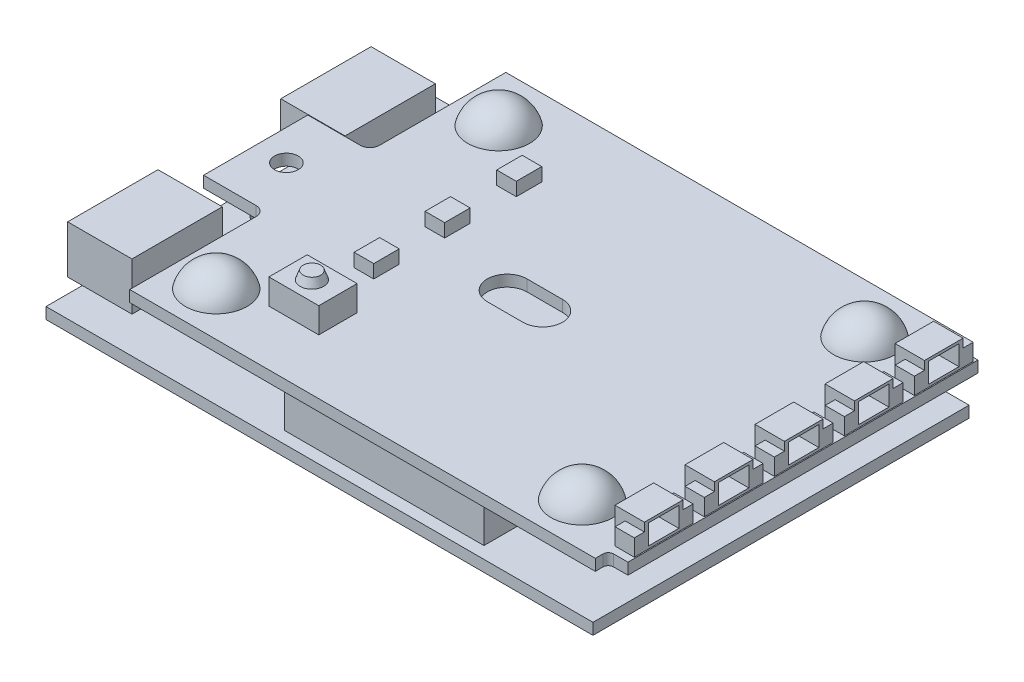
SolidWorks part; units mm, degrees
ref_plane "Front Plane" through (0, 0, 0) normal (0, 0, 1) x (1, 0, 0)
ref_plane "Top Plane" through (0, 0, 0) normal (0, 1, 0) x (1, 0, 0)
ref_plane "Right Plane" through (0, 0, 0) normal (1, 0, 0) x (0, 0, -1)
sketch "Sketch1" plane through (0, 0, 0) normal (0, 1, 0) x (1, 0, 0)
  line L1 (0, 0) -> (77.978, 0)
  line L2 (0, 0) -> (0, -53.6194)
  line L3 (0, -53.6194) -> (77.978, -53.6194)
  line L4 (77.978, 0) -> (77.978, -53.6194)
  dimension "D1" = 77.978
  dimension "D2" = 53.6194
extrude "Bottom Board" add sketch "Sketch1" along normal blind 1.6129
sketch "Sketch2" plane through (0, 1.6129, 0) normal (0, 1, 0) x (-1, 0, 0)
  line L0 (0, 0) -> (0, 53.6194) construction
  line L1 (2.0955, 5.1816) -> (-7.0739, 5.1816)
  line L2 (2.0955, 5.1816) -> (2.0955, 18.0594)
  line L3 (2.0955, 18.0594) -> (-7.0739, 18.0594)
  line L4 (-7.0739, 5.1816) -> (-7.0739, 18.0594)
  line L5 (-77.978, 0) -> (0, 0) construction
  dimension "D1" = 12.8778
  dimension "D2" = 9.1694
  dimension "D3" = 5.1816
  dimension "D4" = 2.0955
extrude "Connector Body" add sketch "Sketch2" along normal blind 6.8199
sketch "Sketch4" plane through (-2.0955, 0, 0) normal (-1, 0, 0) x (0, 0, 1)
  line L0 (5.1816, 8.4328) -> (5.1816, 1.6129) construction
  line L1 (5.7658, 7.8105) -> (8.3947, 7.8105)
  line L2 (5.7658, 7.8105) -> (5.7658, 5.2197)
  line L3 (5.7658, 5.2197) -> (8.3947, 5.2197)
  line L4 (8.3947, 7.8105) -> (8.3947, 5.2197)
  line L5 (5.1816, 8.4328) -> (18.0594, 8.4328) construction
  line L6 (8.7926, 7.8105) -> (8.7926, 5.2197)
  line L7 (8.7926, 5.2197) -> (11.4215, 5.2197)
  line L8 (11.4215, 7.8105) -> (11.4215, 5.2197)
  line L9 (8.7926, 7.8105) -> (11.4215, 7.8105)
  line L10 (11.8195, 7.8105) -> (11.8195, 5.2197)
  line L11 (11.8195, 5.2197) -> (14.4484, 5.2197)
  line L12 (14.4484, 7.8105) -> (14.4484, 5.2197)
  line L13 (11.8195, 7.8105) -> (14.4484, 7.8105)
  line L14 (14.8463, 7.8105) -> (14.8463, 5.2197)
  line L15 (14.8463, 5.2197) -> (17.4752, 5.2197)
  line L16 (17.4752, 7.8105) -> (17.4752, 5.2197)
  line L17 (14.8463, 7.8105) -> (17.4752, 7.8105)
  line L18 (5.7658, 4.826) -> (5.7658, 2.2352)
  line L19 (5.7658, 2.2352) -> (8.3947, 2.2352)
  line L20 (8.3947, 4.826) -> (8.3947, 2.2352)
  line L21 (5.7658, 4.826) -> (8.3947, 4.826)
  line L22 (8.7926, 4.826) -> (8.7926, 2.2352)
  line L23 (8.7926, 2.2352) -> (11.4215, 2.2352)
  line L24 (11.4215, 4.826) -> (11.4215, 2.2352)
  line L25 (8.7926, 4.826) -> (11.4215, 4.826)
  line L26 (11.8195, 4.826) -> (11.8195, 2.2352)
  line L27 (11.8195, 2.2352) -> (14.4484, 2.2352)
  line L28 (14.4484, 4.826) -> (14.4484, 2.2352)
  line L29 (11.8195, 4.826) -> (14.4484, 4.826)
  line L30 (14.8463, 4.826) -> (14.8463, 2.2352)
  line L31 (14.8463, 2.2352) -> (17.4752, 2.2352)
  line L32 (17.4752, 4.826) -> (17.4752, 2.2352)
  line L33 (14.8463, 4.826) -> (17.4752, 4.826)
  line L34 (18.0594, 8.4328) -> (18.0594, 1.6129) construction
  line L35 (17.4752, 7.4085) -> (18.0594, 7.4085) construction
  line L36 (5.7658, 7.5345) -> (5.1816, 7.5345) construction
  line L37 (7.8077, 7.8105) -> (7.8077, 8.4328)
  line L38 (7.8077, 2.2352) -> (7.8077, 1.6129)
  line L39 (5.1816, 1.6129) -> (18.0594, 1.6129) construction
  dimension "D1" = 2.6289
  dimension "D2" = 2.5908
  dimension "D3" = 0.5842
  dimension "D4" = 0.6223
  dimension "D5" = 4
  dimension "D6" = 2
extrude "Connector Holes" cut sketch "Sketch4" against normal blind 5.08 contours L4 L1 L2 L3 | L9 L6 L7 L8 | L13 L10 L11 L12 | L17 L14 L15 L16 | L33 L30 L31 L32 | L29 L26 L27 L28 | L25 L22 L23 L24 | L21 L18 L19 L20 region at (-2.0955, 6.5151, 7.0802) region at (-2.0955, 6.5151, 10.1071) region at (-2.0955, 6.5151, 13.1339) region at (-2.0955, 6.5151, 16.1608) region at (-2.0955, 3.5306, 7.0802) region at (-2.0955, 3.5306, 10.1071) region at (-2.0955, 3.5306, 13.1339) region at (-2.0955, 3.5306, 16.1608)
ref_plane "Center Plane" through (0, 0, 26.8097) normal (0, 0, -1) x (-1, 0, 0)
mirror "Connector Mirror" about plane through (0, 0, 26.8097) normal (0, 0, -1) of "Connector Holes", "Connector Body"
sketch "Sketch5" plane through (0, 1.6129, 0) normal (0, 1, 0) x (1, 0, 0)
  line L0 (77.978, -26.8097) -> (0, -26.8097) construction
  line L1 (77.978, -53.6194) -> (77.978, 0) construction
  line L2 (0, -18.0594) -> (0, -35.56) construction
  line L3 (2.9845, -26.8097) -> (2.9845, -21.4955) construction
  line L4 (36.0172, -26.8097) -> (36.0172, -8.1241) construction
  line L5 (0, -18.0594) -> (0, -35.56) construction
  circle A0 centre (4.68, -26.8097) radius 1.6955
  circle A1 centre (39.0652, -26.8097) radius 3.048
  dimension "D1" = 3.3909
  dimension "D3" = 6.096
  dimension "D2" = 2.9845
  dimension "D4" = 36.0172
extrude "Bottom Board Hole" cut sketch "Sketch5" against normal up to next
sketch "Sketch6" plane through (0, 1.6129, 0) normal (0, 1, 0) x (-1, 0, 0)
  line L0 (-77.978, 0) -> (0, 0) construction
  line L1 (-39.37, 1.7018) -> (-67.818, 1.7018)
  line L2 (-39.37, 1.7018) -> (-39.37, 7.2644)
  line L3 (-39.37, 7.2644) -> (-67.818, 7.2644)
  line L4 (-67.818, 1.7018) -> (-67.818, 7.2644)
  line L5 (-77.978, 53.6194) -> (-77.978, 0) construction
  line L6 (-32.2834, 46.355) -> (-60.7314, 46.355)
  line L7 (-32.2834, 46.355) -> (-32.2834, 51.9176)
  line L8 (-32.2834, 51.9176) -> (-60.7314, 51.9176)
  line L9 (-60.7314, 46.355) -> (-60.7314, 51.9176)
  line L10 (0, 18.0594) -> (0, 35.56) construction
  line L12 (-44.4047, 1.7018) -> (-44.4047, 0) construction
  line L13 (-37.561, 51.9176) -> (-37.561, 53.6194) construction
  line L14 (0, 53.6194) -> (-77.978, 53.6194) construction
  dimension "D1" = 28.448
  dimension "D2" = 5.5626
  dimension "D3" = 1.7018
  dimension "D4" = 10.16
  dimension "D5" = 28.448
  dimension "D6" = 5.5626
  dimension "D7" = 32.2834
extrude "Layer Connectors" add sketch "Sketch6" along normal blind 6.4516
sketch "Sketch7" plane through (0, 8.0645, 0) normal (0, 1, 0) x (1, 0, 0)
  line L0 (77.978, -53.6194) -> (77.978, 0) construction
  line L1 (78.3082, 0) -> (11.938, 0)
  line L2 (81.1022, -1.8542) -> (81.1022, -51.7652)
  line L3 (78.3082, -53.6194) -> (11.938, -53.6194)
  line L4 (11.938, 0) -> (11.938, -18.0086)
  line L5 (0, -18.0594) -> (0, -35.56) construction
  line L6 (77.978, 0) -> (0, 0) construction
  line L7 (0, -53.6194) -> (77.978, -53.6194) construction
  line L8 (15.6034, 0) -> (15.6034, -19.3802) construction
  line L9 (10.5664, -19.3802) -> (3.0861, -19.3802)
  line L10 (11.938, -35.6108) -> (11.938, -53.6194)
  line L11 (10.5664, -34.2392) -> (3.0861, -34.2392)
  line L12 (3.0861, -19.3802) -> (3.0861, -34.2392)
  line L13 (10.5664, -19.3802) -> (15.6034, -19.3802) construction
  line L14 (16.8171, -34.2392) -> (16.8171, -53.6194) construction
  line L15 (10.5664, -34.2392) -> (16.8171, -34.2392) construction
  line L16 (77.978, -26.8097) -> (0, -26.8097) construction
  line L17 (5.7658, -26.8097) -> (5.7658, -22.9762) construction
  line L18 (36.1061, -26.8097) -> (46.8249, -26.8097) construction
  line L19 (38.9318, -23.984) -> (43.9992, -23.984)
  line L20 (36.1061, -26.8097) -> (36.1061, -33.1542) construction
  line L21 (38.9318, -29.6354) -> (43.9992, -29.6355)
  line L22 (78.3082, -53.6194) -> (78.3082, -52.5272)
  line L23 (81.1022, -51.7652) -> (79.0702, -51.7652)
  line L25 (81.1022, -1.8542) -> (79.0702, -1.8542)
  line L26 (78.3082, 0) -> (78.3082, -1.0922)
  arc A0 (11.938, -18.0086) -> (10.5664, -19.3802) centre (10.5664, -18.0086) cw
  arc A1 (10.5664, -34.2392) -> (11.938, -35.6108) centre (10.5664, -35.6108) cw
  circle A2 centre (7.4613, -26.8097) radius 1.6955
  circle A3 centre (4.68, -26.8097) radius 1.6955 construction
  arc A4 (38.9318, -29.6354) -> (38.9318, -23.984) centre (38.9318, -26.8097) cw
  arc A5 (43.9992, -23.984) -> (43.9992, -29.6355) centre (43.9992, -26.8097) cw
  arc A6 (79.0702, -1.8542) -> (78.3082, -1.0922) centre (79.0702, -1.0922) cw
  arc A7 (79.0702, -51.7652) -> (78.3082, -52.5272) centre (79.0702, -52.5272) ccw
  point P45 (78.3082, -1.8542)
  dimension "D5" = 1.3716
  dimension "D6" = 1.3716
  dimension "D13" = 0.762
  dimension "D1" = 3.1242
  dimension "D2" = 11.938
  dimension "D3" = 19.3802
  dimension "D4" = 3.0861
  dimension "D7" = 2.6797
  dimension "D8" = 5.6515
  dimension "D9" = 10.7188
  dimension "D10" = 33.02
  dimension "D11" = 2.794
  dimension "D12" = 1.8542
extrude "Top Board" add sketch "Sketch7" along normal blind 1.6129
sketch "Sketch8" plane through (0, 9.6774, 0) normal (0, 1, 0) x (1, 0, 0)
  line L1 (80.9498, -2.3876) -> (78.2066, -2.3876)
  line L2 (80.9498, -2.3876) -> (80.9498, -10.7696)
  line L3 (80.9498, -10.7696) -> (78.2066, -10.7696)
  line L4 (78.2066, -2.3876) -> (78.2066, -10.7696)
  line L5 (78.3082, 0) -> (11.938, 0) construction
  line L6 (81.1022, -51.7652) -> (81.1022, -1.8542) construction
  dimension "D1" = 2.7432
  dimension "D2" = 8.382
  dimension "D3" = 2.3876
  dimension "D4" = 0.1524
extrude "Maker Connector Sides" add sketch "Sketch8" along normal blind 2.3876
sketch "Sketch9" plane through (0, 12.065, 0) normal (0, 1, 0) x (1, 0, 0)
  line L0 (80.9498, -10.7696) -> (80.9498, -2.3876) construction
  line L1 (80.9498, -3.8227) -> (76.7588, -3.8227)
  line L2 (80.9498, -3.8227) -> (80.9498, -9.3345)
  line L3 (80.9498, -9.3345) -> (76.7588, -9.3345)
  line L4 (76.7588, -3.8227) -> (76.7588, -9.3345)
  line L6 (78.7411, -2.3876) -> (78.7411, -3.8227) construction
  line L7 (80.9498, -2.3876) -> (78.2066, -2.3876) construction
  line L9 (78.7411, -9.3345) -> (78.7411, -10.7696) construction
  line L10 (78.2066, -10.7696) -> (80.9498, -10.7696) construction
  dimension "D1" = 5.5118
  dimension "D2" = 4.191
extrude "Marker Connector Box" add sketch "Sketch9" along normal blind 1.2192
sketch "Sketch10" plane through (0, 9.6774, 0) normal (0, 1, 0) x (1, 0, 0)
  line L0 (76.7588, -9.3345) -> (78.2066, -9.3345) construction
  line L1 (78.2066, -3.8227) -> (76.7588, -3.8227) construction
  line L2 (76.7588, -3.8227) -> (76.7588, -9.3345) construction
  line L3 (76.7588, -9.3345) -> (78.2066, -9.3345)
  line L4 (78.2066, -3.8227) -> (76.7588, -3.8227)
  line L5 (76.7588, -3.8227) -> (76.7588, -9.3345)
  line L10 (78.2066, -3.8227) -> (76.7588, -3.8227)
  line L11 (78.2066, -9.3345) -> (78.2066, -3.8227)
  line L12 (76.7588, -9.3345) -> (78.2066, -9.3345)
  line L13 (76.7588, -3.8227) -> (76.7588, -9.3345)
  line L14 (78.2066, -3.8227) -> (76.7588, -3.8227)
  line L15 (78.2066, -9.3345) -> (78.2066, -3.8227)
  line L16 (76.7588, -9.3345) -> (78.2066, -9.3345)
  line L17 (76.7588, -3.8227) -> (76.7588, -9.3345)
  line M11 (78.2066, -10.7696) -> (78.2066, -2.3876)
  dimension "D1" = 0
extrude "Marker Connector Rear" add sketch "Sketch10" along normal up to body contours L4 L5 L3 M11 region at (77.4827, 9.6774, 6.5786)
sketch "Sketch11" plane through (81.1022, 0, 0) normal (1, 0, 0) x (0, 0, -1)
  line L0 (-9.3345, 13.2842) -> (-9.3345, 12.065) construction
  line L1 (-8.7376, 12.9032) -> (-4.4196, 12.9032)
  line L2 (-8.7376, 12.9032) -> (-8.7376, 10.0584)
  line L3 (-8.7376, 10.0584) -> (-4.4196, 10.0584)
  line L4 (-4.4196, 12.9032) -> (-4.4196, 10.0584)
  line L5 (-8.7376, 11.497) -> (-9.3345, 11.497) construction
  line L6 (-4.4196, 12.3526) -> (-3.8227, 12.3526) construction
  line L7 (-3.8227, 13.2842) -> (-3.8227, 12.065) construction
  line L8 (-9.3345, 13.2842) -> (-3.8227, 13.2842) construction
  line L10 (-7.3098, 10.0584) -> (-7.3098, 9.6774) construction
  line L11 (-51.7652, 9.6774) -> (-1.8542, 9.6774) construction
  line L12 (-7.3098, 13.2842) -> (-7.3098, 12.9032) construction
  dimension "D1" = 0.5969
  dimension "D2" = 0.381
extrude "Marker Connector " cut sketch "Sketch11" against normal blind 3.175
pattern_linear "Maker Connectors Pattern" count 5 spacing 9.9822 along (0, 0, 1) of "Marker Connector Box", "Marker Connector ", "Maker Connector Sides", "Marker Connector Rear"
sketch "Sketch12" plane through (0, 9.6774, 0) normal (0, 1, 0) x (-1, 0, 0)
  line L0 (-13.589, 7.0866) -> (-13.589, -6.6902) construction
  line L1 (-11.938, 0) -> (-11.938, 18.0086) construction
  line L2 (-17.9959, 2.6797) -> (-29.745, 2.6797) construction
  line L3 (-78.3082, 0) -> (-11.938, 0) construction
  circle A0 centre (-17.9959, 7.0866) radius 4.4069
  dimension "D1" = 8.8138
  dimension "D2" = 1.651
  dimension "D3" = 2.6797
extrude "Glue Dome" add sketch "Sketch12" along normal blind 3.4036
fillet "Glue Dome Fillet" radius 4.5415 1 edges at (17.9959, 13.081, 11.4935)
pattern_linear "Glue pattern" count 2 spacing 40.259 along (0, 0, 1) count 2 spacing 52.1462 along (1, 0, 0) of "Glue Dome Fillet", "Glue Dome"
sketch "Sketch13" plane through (0, 9.6774, 0) normal (0, 1, 0) x (-1, 0, 0)
  line L0 (-78.3082, 0) -> (-11.938, 0) construction
  line L1 (-25.2349, 10.9728) -> (-28.0289, 10.9728)
  line L2 (-25.2349, 10.9728) -> (-25.2349, 14.605)
  line L3 (-25.2349, 14.605) -> (-28.0289, 14.605)
  line L4 (-28.0289, 10.9728) -> (-28.0289, 14.605)
  line L5 (-3.0861, 19.3802) -> (-3.0861, 34.2392) construction
  line L7 (-25.2349, 21.1836) -> (-28.0289, 21.1836)
  line L8 (-25.2349, 21.1836) -> (-25.2349, 24.8158)
  line L9 (-25.2349, 24.8158) -> (-28.0289, 24.8158)
  line L10 (-28.0289, 21.1836) -> (-28.0289, 24.8158)
  line L11 (-25.2349, 31.2928) -> (-28.0289, 31.2928)
  line L12 (-25.2349, 31.2928) -> (-25.2349, 34.925)
  line L13 (-25.2349, 34.925) -> (-28.0289, 34.925)
  line L14 (-28.0289, 31.2928) -> (-28.0289, 34.925)
  dimension "D1" = 2.794
  dimension "D2" = 3.6322
  dimension "D3" = 10.9728
  dimension "D4" = 22.1488
  dimension "D5" = 24.8158
  dimension "D6" = 34.925
extrude "LEDs" add sketch "Sketch13" along normal blind 1.905
sketch "Sketch14" plane through (0, 9.6774, 0) normal (0, 1, 0) x (-1, 0, 0)
  line L0 (-11.938, 53.6194) -> (-78.3082, 53.6194) construction
  line L1 (-23.9014, 40.2844) -> (-31.0134, 40.2844)
  line L2 (-23.9014, 40.2844) -> (-23.9014, 45.7454)
  line L3 (-23.9014, 45.7454) -> (-31.0134, 45.7454)
  line L4 (-31.0134, 40.2844) -> (-31.0134, 45.7454)
  line L5 (-81.1022, 51.7652) -> (-81.1022, 1.8542) construction
  dimension "D1" = 7.112
  dimension "D2" = 5.461
  dimension "D3" = 7.874
  dimension "D4" = 50.0888
extrude "IR receiver base" add sketch "Sketch14" along normal blind 3.6068
sketch "Sketch16" plane through (0, 13.2842, 0) normal (0, 1, 0) x (-1, 0, 0)
  line L0 (-27.305, 40.2844) -> (-27.305, 45.7454) construction
  line L3 (-31.0134, 40.2844) -> (-23.9014, 40.2844) construction
  line L4 (-23.9014, 45.7454) -> (-31.0134, 45.7454) construction
  line L5 (-28.9814, 43.0149) -> (-28.9814, 38.6964) construction
  line L6 (-23.9014, 40.2844) -> (-23.9014, 45.7454) construction
  circle A0 centre (-27.305, 43.0149) radius 1.6764
  circle A1 centre (-27.305, 43.0149) radius 1.2446 construction
  dimension "D1" = 3.3528
  dimension "D2" = 2.4892
  dimension "D3" = 5.08
ref_plane "Plane for IR receiver" through (0, 14.4526, 0) normal (0, 1, 0) x (-1, 0, 0)
sketch "Sketch17" plane through (0, 14.4526, 0) normal (0, 1, 0) x (-1, 0, 0)
  circle A0 centre (-27.305, 43.0149) radius 1.2446 construction
  circle A3 centre (-27.305, 43.0149) radius 1.2446
loft "IR receiver" add profiles "Sketch16", "Sketch17" connector at (28.1584, 13.2842, 44.4578) connector at (27.9456, 14.4526, 44.082)
sketch "Sketch18" plane through (0, 0, 0) normal (0, -1, 0) x (1, 0, 0)
  line L0 (0, 53.6194) -> (77.978, 53.6194) construction
  line L1 (15.2908, 49.5554) -> (18.0848, 49.5554)
  line L2 (15.2908, 49.5554) -> (15.2908, 44.5262)
  line L3 (15.2908, 44.5262) -> (18.0848, 44.5262)
  line L4 (18.0848, 49.5554) -> (18.0848, 44.5262)
  line L5 (0, 0) -> (0, 53.6194) construction
  line L6 (15.2908, 42.7228) -> (18.0848, 42.7228)
  line L7 (15.2908, 42.7228) -> (15.2908, 37.6936)
  line L8 (15.2908, 37.6936) -> (18.0848, 37.6936)
  line L9 (18.0848, 42.7228) -> (18.0848, 37.6936)
  line L10 (77.978, 0) -> (0, 0) construction
  line L11 (20.32, 36.0934) -> (23.114, 36.0934)
  line L12 (20.32, 36.0934) -> (20.32, 31.0642)
  line L13 (20.32, 31.0642) -> (23.114, 31.0642)
  line L14 (23.114, 36.0934) -> (23.114, 31.0642)
  dimension "D1" = 2.794
  dimension "D2" = 5.0292
  dimension "D3" = 4.064
  dimension "D4" = 15.2908
  dimension "D5" = 2.794
  dimension "D6" = 5.0292
  dimension "D7" = 37.6936
  dimension "D8" = 2.794
  dimension "D9" = 5.0292
  dimension "D10" = 20.32
  dimension "D11" = 17.526
extrude "Back components" add sketch "Sketch18" along normal blind 2.4892
sketch "Sketch19" plane through (0, 0, 0) normal (0, -1, 0) x (1, 0, 0)
  line L0 (0, 53.6194) -> (77.978, 53.6194) construction
  line L1 (36.3093, 43.5864) -> (38.0873, 43.5864)
  line L2 (36.3093, 43.5864) -> (36.3093, 40.513)
  line L3 (36.3093, 40.513) -> (38.0873, 40.513)
  line L4 (38.0873, 43.5864) -> (38.0873, 40.513)
  line L5 (77.978, 53.6194) -> (77.978, 0) construction
  line L6 (40.3606, 37.338) -> (42.1386, 37.338)
  line L7 (40.3606, 37.338) -> (40.3606, 34.2646)
  line L8 (40.3606, 34.2646) -> (42.1386, 34.2646)
  line L9 (42.1386, 37.338) -> (42.1386, 34.2646)
  dimension "D1" = 1.778
  dimension "D2" = 3.0734
  dimension "D3" = 10.033
  dimension "D4" = 39.8907
  dimension "D5" = 1.778
  dimension "D6" = 16.2814
  dimension "D7" = 35.8394
extrude "Bottom caps" add sketch "Sketch19" along normal blind 1.7526
